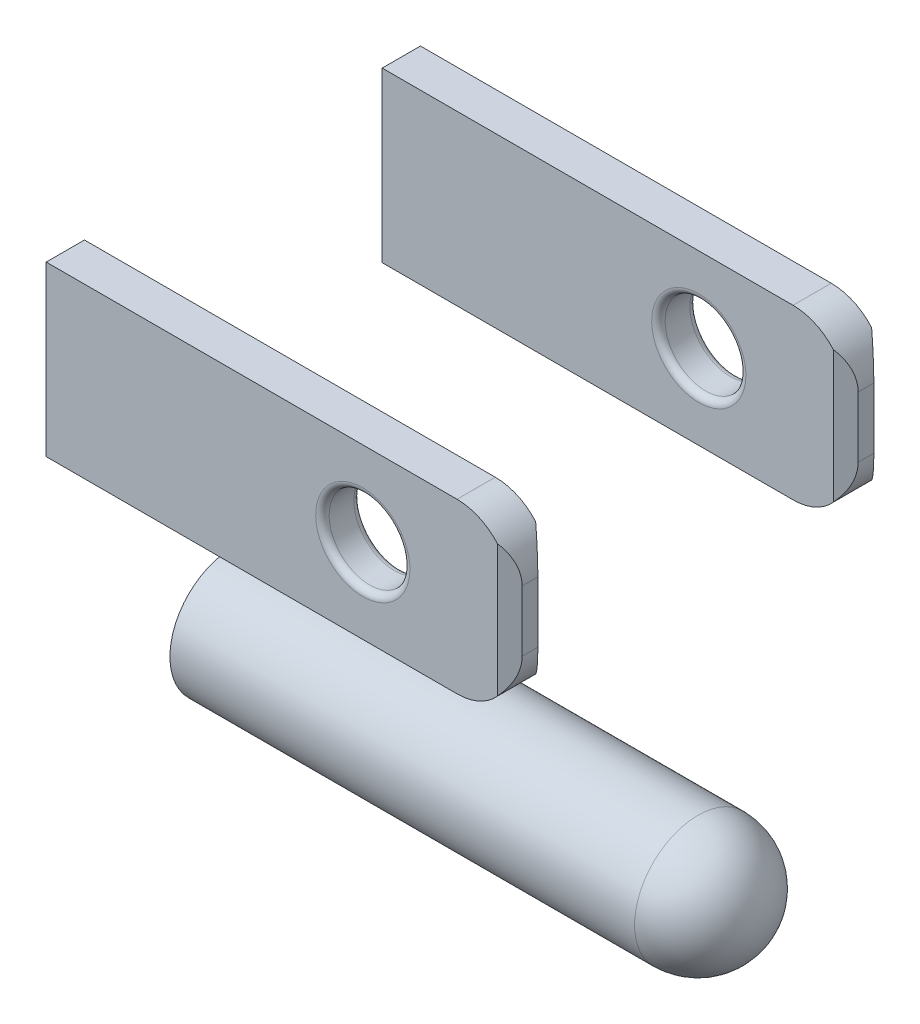
SolidWorks part; units mm, degrees
ref_plane "Front Plane" through (0, 0, 0) normal (0, 0, 1) x (1, 0, 0)
ref_plane "Top Plane" through (0, 0, 0) normal (0, 1, 0) x (1, 0, 0)
ref_plane "Right Plane" through (0, 0, 0) normal (1, 0, 0) x (0, 0, -1)
sketch "Sketch1" plane through (0, 0, 0) normal (1, 0, 0) x (0, 0, -1)
  line L0 (6.95, 6.935) -> (5.53, 6.935) construction
  line L1 (5.53, 6.935) -> (5.53, 0.675) construction
  line L2 (5.53, 0.675) -> (6.95, 0.675) construction
  line L3 (6.95, 0.675) -> (6.95, 6.935) construction
  line L4 (-5.53, 6.935) -> (-6.95, 6.935) construction
  line L5 (-6.95, 6.935) -> (-6.95, 0.675) construction
  line L6 (-6.95, 0.675) -> (-5.53, 0.675) construction
  line L7 (-5.53, 0.675) -> (-5.53, 6.935) construction
  line L8 (6.95, 6.935) -> (5.53, 6.935)
  line L9 (5.53, 6.935) -> (5.53, 0.675)
  line L10 (5.53, 0.675) -> (6.95, 0.675)
  line L11 (6.95, 0.675) -> (6.95, 6.935)
  line L12 (-5.53, 6.935) -> (-6.95, 6.935)
  line L13 (-6.95, 6.935) -> (-6.95, 0.675)
  line L14 (-6.95, 0.675) -> (-5.53, 0.675)
  line L15 (-5.53, 0.675) -> (-5.53, 6.935)
  circle A0 centre (0, -8.06) radius 2.355 construction
  circle A1 centre (0, -8.06) radius 2.355
extrude "Boss-Extrude1" add sketch "Sketch1" along normal blind 17.26
chamfer "Chamfer1" distance 0.5 angle 40 2 edges at (17.26, 3.805, 6.95) (17.26, 3.805, 5.53) first distance on face at (8.63, 3.805, 6.95) first distance on face at (8.63, 3.805, 5.53)
chamfer "Chamfer2" distance 0.5 angle 40 2 edges at (17.26, 3.805, -6.95) (17.26, 3.805, -5.53) first distance on face at (8.63, 3.805, -6.95) first distance on face at (8.63, 3.805, -5.53)
fillet "Fillet1" radius 2 2 edges at (17.26, 6.935, 6.24) (17.26, 0.675, 6.24)
fillet "Fillet2" radius 2 2 edges at (17.26, 0.675, -6.24) (17.26, 6.935, -6.24)
dome "Dome1" faces to dome 1 distance 2.35 reverse direction no elliptical dome no face at (17.26, -8.06, -2.355) parameters "D1"=2.35
sketch "Sketch2" plane through (0, 0, 6.95) normal (0, 0, 1) x (1, 0, 0)
  line L0 (17.26, 3.805) -> (11.76, 3.805) construction
  line L1 (17.26, 4.935) -> (17.26, 2.675) construction
  line L2 (10.26, 6.2964) -> (10.26, 1.7976) construction
  circle A0 centre (11.76, 3.805) radius 1.5
  dimension "D1" = 3
  dimension "D2" = 7
extrude "Cut-Extrude1" cut sketch "Sketch2" against normal blind 21
fillet "Fillet3" radius 0.25 2 edges at (11.76, 5.305, -5.53) (11.76, 2.305, -6.95)
fillet "Fillet4" radius 0.25 2 edges at (13.26, 3.805, 6.95) (11.76, 2.305, 5.53)
